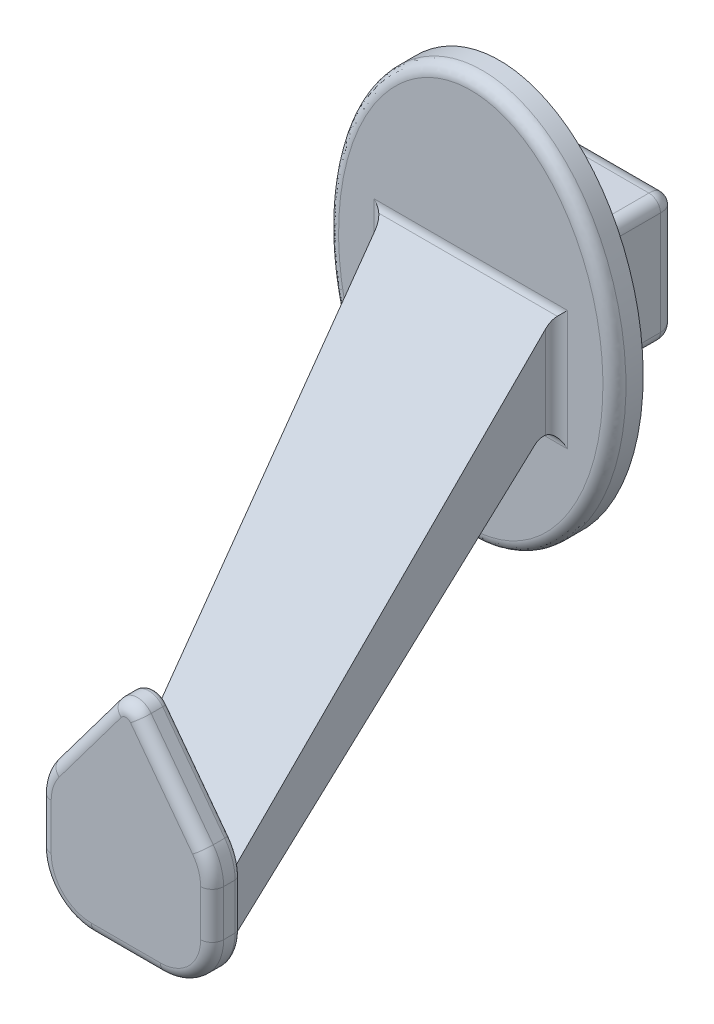
SolidWorks part; units mm, degrees
ref_plane "Front Plane" through (0, 0, 0) normal (0, 0, 1) x (1, 0, 0)
ref_plane "Top Plane" through (0, 0, 0) normal (0, 1, 0) x (1, 0, 0)
ref_plane "Right Plane" through (0, 0, 0) normal (1, 0, 0) x (0, 0, -1)
sketch "Sketch1" plane through (0, 0, 0) normal (0, 0, 1) x (1, 0, 0)
  ellipse E0 centre (0, 0) end of major axis (0, -8.89) minor radius 6.35
  dimension "D1" = 17.78
  dimension "D2" = 12.7
extrude "Boss-Extrude1" add sketch "Sketch1" along normal blind 1.27
sketch "Sketch2" plane through (0, 0, 1.27) normal (0, 0, 1) x (1, 0, 0)
  line L1 (-3.81, 1.905) -> (3.81, 1.905)
  line L2 (-3.81, 1.905) -> (-3.81, -1.905)
  line L3 (-3.81, -1.905) -> (3.81, -1.905)
  line L4 (3.81, 1.905) -> (3.81, -1.905)
  line L5 (-3.81, 1.905) -> (3.81, -1.905) construction
  line L6 (-3.81, -1.905) -> (3.81, 1.905) construction
  point P0 (0, 0)
  dimension "D1" = 7.62
  dimension "D2" = 3.81
ref_plane "Plane1" through (0, 0, 15.24) normal (0, 0, 1) x (1, 0, 0)
sketch "Sketch3" plane through (0, 0, 15.24) normal (0, 0, 1) x (1, 0, 0)
  line L0 (-3.81, -1.905) -> (3.81, -1.905) construction
  line L1 (-2.54, -14.605) -> (2.54, -14.605)
  line L2 (-2.54, -14.605) -> (-2.54, -17.145)
  line L3 (-2.54, -17.145) -> (2.54, -17.145)
  line L4 (2.54, -14.605) -> (2.54, -17.145)
  line L5 (-2.54, -14.605) -> (2.54, -17.145) construction
  line L6 (-2.54, -17.145) -> (2.54, -14.605) construction
  point P0 (0, -15.875)
  dimension "D1" = 5.08
  dimension "D2" = 2.54
  dimension "D3" = 15.24
loft "Loft1" add profiles "Sketch3", "Sketch2" connector at (2.54, -14.605, 15.24) connector at (3.81, 1.905, 1.27)
sketch "Sketch4" plane through (0, 0, 15.24) normal (0, 0, 1) x (1, 0, 0)
  line L0 (-3.81, -12.065) -> (0, -6.985)
  line L1 (0, -6.985) -> (3.81, -12.065)
  line L3 (-2.54, -17.145) -> (2.54, -17.145) construction
  line L8 (3.81, -17.145) -> (3.81, -12.065)
  line L10 (-3.81, -12.065) -> (-3.81, -17.145)
  line L11 (-3.81, -17.145) -> (3.81, -17.145)
  dimension "D2" = 10.16
  dimension "D3" = 7.62
  dimension "D1" = 7.62
  dimension "D4" = 5.08
  dimension "D5" = 53.13
  dimension "D6" = 53.13
extrude "Boss-Extrude2" add sketch "Sketch4" along normal blind 1.27
fillet "Fillet1" radius 0.508 1 edges at (0, -8.89, 1.27)
fillet "Fillet2" radius 0.508 4 edges
fillet "Fillet3" radius 2.286 4 edges at (3.81, -17.145, 15.875) (3.81, -12.065, 15.875) (-3.81, -17.145, 15.875) (-3.81, -12.065, 15.875)
fillet "Fillet4" radius 0.762 1 edges at (0, -6.985, 15.875)
fillet "Fillet5" radius 0.762 2 edges
fillet "Fillet6" radius 0.254 11 edges at (-3.1248, -16.4909, 15.198) (-3.6984, -15.5646, 15.24) (-3.81, -13.843, 15.24) (-3.6927, -12.1041, 15.24) (-1.9812, -9.6266, 15.24) (0, -7.493, 15.24) (1.9812, -9.6266, 15.24) (3.6927, -12.1041, 15.24) (3.81, -13.843, 15.24) (2.9177, -16.671, 15.088) (3.6984, -15.5646, 15.24)
fillet "Fillet7" radius 0.508 10 edges at (0, -7.493, 16.51) (1.9812, -9.6266, 16.51) (3.6927, -12.1041, 16.51) (3.81, -13.843, 16.51) (3.1404, -16.4754, 16.51) (0, -17.145, 16.51) (-3.1404, -16.4754, 16.51) (-3.81, -13.843, 16.51) (-3.6927, -12.1041, 16.51) (-1.9812, -9.6266, 16.51)
sketch "Sketch5" plane through (0, 0, 0) normal (0, 0, -1) x (-1, 0, 0)
  point P0 (0, 0)
sketch "Sketch6" plane through (0, 0, 0) normal (0, 0, -1) x (-1, 0, 0)
  line L1 (-2.286, 2.794) -> (2.286, 2.794)
  line L2 (-2.794, 2.286) -> (-2.794, -2.286)
  line L3 (-2.286, -2.794) -> (2.286, -2.794)
  line L4 (2.794, 2.286) -> (2.794, -2.286)
  line L5 (-2.794, 2.794) -> (2.794, -2.794) construction
  line L6 (-2.794, -2.794) -> (2.794, 2.794) construction
  arc A0 (-2.794, -2.286) -> (-2.286, -2.794) centre (-2.286, -2.286) ccw
  arc A1 (2.286, -2.794) -> (2.794, -2.286) centre (2.286, -2.286) ccw
  arc A2 (2.286, 2.794) -> (2.794, 2.286) centre (2.286, 2.286) cw
  arc A3 (-2.286, 2.794) -> (-2.794, 2.286) centre (-2.286, 2.286) ccw
  point P0 (0, 0)
  dimension "D3" = 0.508
  dimension "D1" = 5.588
  dimension "D2" = 5.588
extrude "Boss-Extrude3" add sketch "Sketch6" along normal blind 5.08
fillet "Fillet8" radius 0.762 8 edges at (2.6452, 2.6452, -5.08) (0, 2.794, -5.08) (-2.6452, 2.6452, -5.08) (-2.794, 0, -5.08) (-2.6452, -2.6452, -5.08) (0, -2.794, -5.08) (2.6452, -2.6452, -5.08) (2.794, 0, -5.08)
ref_axis "Axis1" through (-3.81, -12.827, 16.002) along (1, 0, 0)
